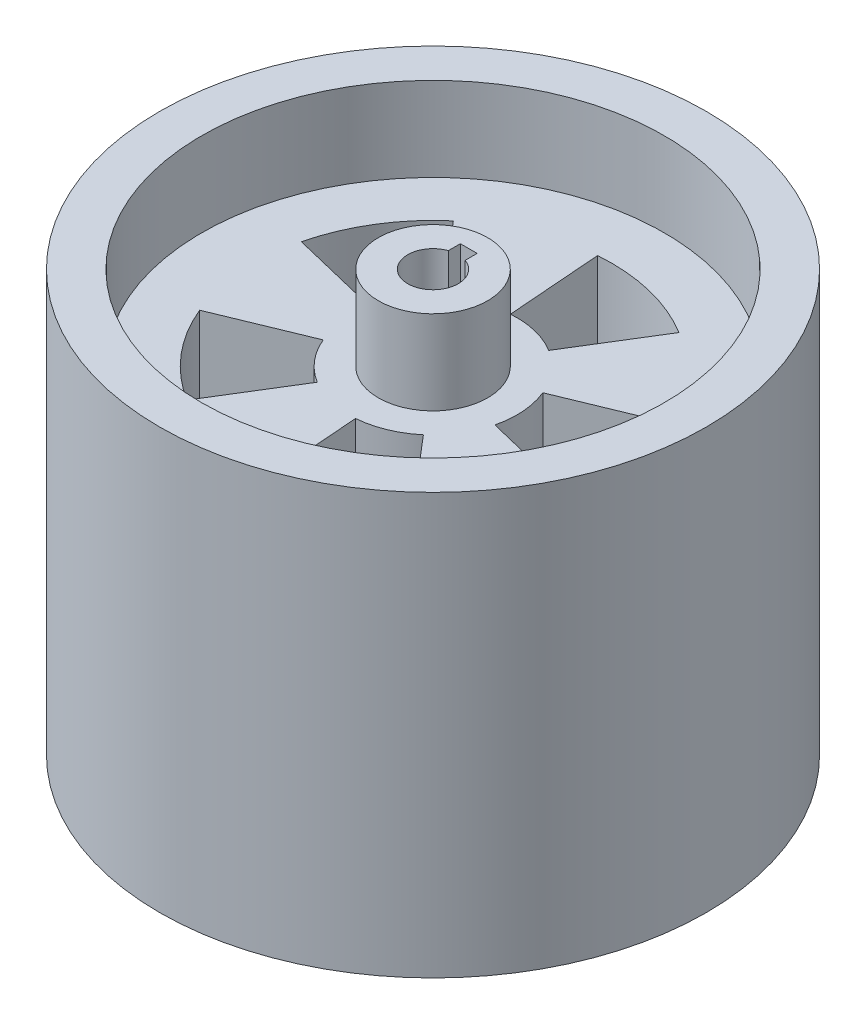
SolidWorks part; units mm, degrees
material "Plain Carbon Steel"
ref_plane "Front Plane" through (0, 0, 0) normal (0, 0, 1) x (1, 0, 0)
ref_plane "Top Plane" through (0, 0, 0) normal (0, 1, 0) x (1, 0, 0)
ref_plane "Right Plane" through (0, 0, 0) normal (1, 0, 0) x (0, 0, -1)
sketch "Sketch1" plane through (0, 0, 0) normal (0, 1, 0) x (1, 0, 0)
  line L1 (-2.5, 8.5) -> (2.5, 8.5)
  line L2 (-2.5, 8.5) -> (-2.5, 5.4544)
  line L4 (2.5, 8.5) -> (2.5, 5.4544)
  line L5 (-2.5, 8.5) -> (4.1708, 1.8292) construction
  line L6 (-4.1708, 1.8292) -> (2.5, 8.5) construction
  circle A0 centre (0, 0) radius 55
  circle A1 centre (0, 0) radius 65
  arc A2 (-2.5, 5.4544) -> (2.5, 5.4544) centre (0, 0) ccw
  point P4 (0, 8.5)
  point P5 (0, 6)
  dimension "D1" = 5
  dimension "D3" = 12
  dimension "D4" = 130
  dimension "D5" = 110
  dimension "D2" = 2.5
  dimension "D6" = 3.0456
extrude "Boss-Extrude1" add sketch "Sketch1" along normal blind 100 contours A1 A0 region at (-63.1615, 0, 0)
sketch "Sketch3" plane through (0, 0, 0) normal (0, 1, 0) x (1, 0, 0)
  line L1 (41.3049, -10.0079) -> (19.4376, -4.7096)
  line L2 (18.4936, 7.615) -> (39.2988, 16.1819)
  line L3 (19.4376, -4.7096) -> (41.3049, -10.0079)
  line L4 (3.2459, -42.3759) -> (1.5275, -19.9416)
  line L5 (12.9571, -15.2353) -> (27.5339, -32.3749)
  line L6 (-39.2988, -16.1819) -> (-18.4936, -7.615)
  line L7 (-10.4856, -17.0309) -> (-22.2819, -36.1907)
  line L8 (-27.5339, 32.3749) -> (-12.9571, 15.2353)
  line L9 (-19.4376, 4.7096) -> (-41.3049, 10.0079)
  line L10 (22.2819, 36.1907) -> (10.4856, 17.0309)
  line L11 (-1.5275, 19.9416) -> (-3.2459, 42.3759)
  line L18 (2, 5.6569) -> (2, 8.5)
  line L19 (2, 8.5) -> (-2, 8.5)
  line L20 (-2, 5.6569) -> (-2, 8.5)
  line L21 (2.5047, 2.8691) -> (-2, 8.5) construction
  line L22 (2, 8.5) -> (-2.5047, 2.8691) construction
  circle A0 centre (0, 0) radius 6.5
  circle A1 centre (0, 0) radius 55
  arc A2 (41.3049, -10.0079) -> (39.2988, 16.1819) centre (0, 0) ccw
  circle A3 centre (0, 0) radius 20
  circle A4 centre (0, 0) radius 13
  arc A5 (3.2459, -42.3759) -> (27.5339, -32.3749) centre (0, 0) ccw
  arc A6 (-39.2988, -16.1819) -> (-22.2819, -36.1907) centre (0, 0) ccw
  arc A7 (-27.5339, 32.3749) -> (-41.3049, 10.0079) centre (0, 0) ccw
  arc A8 (22.2819, 36.1907) -> (-3.2459, 42.3759) centre (0, 0) ccw
  arc A9 (-2, 5.6569) -> (2, 5.6569) centre (0, 0) ccw
  point P28 (0, 6)
  dimension "D1" = 110
  dimension "D2" = 85
  dimension "D3" = 40
  dimension "D4" = 13
  dimension "D7" = 26
  dimension "D8" = 4
  dimension "D10" = 12
  dimension "D5" = 20.8053
  dimension "D6" = 21.8673
  dimension "D9" = 2.5
  dimension "D11" = 2.8431
extrude "Boss-Extrude2" add sketch "Sketch3" along normal blind 20 from offset 20 contours A1 A8 L10 A3 L2 A2 L1 L5 A5 L4 L7 A6 L6 L9 A7 L8 L11 | A3 A4 region at (16.5492, 0, 10.189) region at (-53.4444, 0, 0)
extrude "Boss-Extrude3" add sketch "Sketch3<5>" along normal blind 20 from offset 60 contours A1 A8 L10 A3 L2 A2 L1 L5 A5 L4 L7 A6 L6 L9 A7 L8 L11 | A3 A4 region at (16.5492, 0, 10.189) region at (-53.4444, 0, 0)
sketch "Sketch3<5>" plane through (0, 0, 0) normal (0, 1, 0) x (1, 0, 0) same geometry as "Sketch3"
extrude "Boss-Extrude4" add sketch "Sketch3<7>" along normal blind 60 from offset 20 contours A4 A0 L20 L19 L18 | A0 L18 L19 L20 region at (0, 0, -7.4459) region at (-12.6323, 0, 0)
sketch "Sketch3<7>" plane through (0, 0, 0) normal (0, 1, 0) x (1, 0, 0) same geometry as "Sketch3"
extrude "Boss-Extrude5" add sketch "Sketch3<10>" along normal blind 20 contours A9 L20 A0 L18 | A4 A0 L20 L19 L18 region at (2.1816, 0, -5.9208) region at (-12.6323, 0, 0)
sketch "Sketch3<10>" plane through (0, 0, 0) normal (0, 1, 0) x (1, 0, 0) same geometry as "Sketch3"
extrude "Boss-Extrude6" add sketch "Sketch3<11>" along normal blind 20 from offset 80 contours A9 L20 A0 L18 | A4 A0 L20 L19 L18 region at (2.1816, 0, -5.9208) region at (-12.6323, 0, 0)
sketch "Sketch3<11>" plane through (0, 0, 0) normal (0, 1, 0) x (1, 0, 0) same geometry as "Sketch3"
